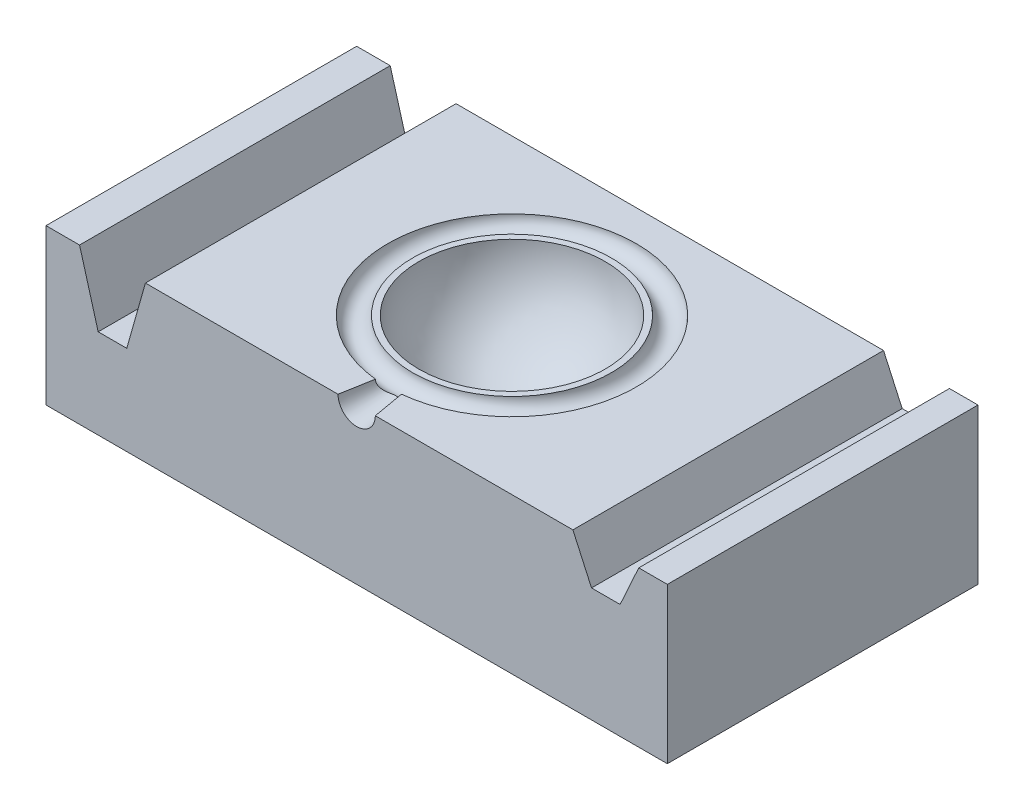
SolidWorks part; units mm, degrees
ref_plane "Plan de face" through (0, 0, 0) normal (0, 0, 1) x (1, 0, 0)
ref_plane "Plan de dessus" through (0, 0, 0) normal (0, 1, 0) x (1, 0, 0)
ref_plane "Plan de droite" through (0, 0, 0) normal (1, 0, 0) x (0, 0, -1)
sketch "Esquisse1" plane through (0, 0, 0) normal (0, 1, 0) x (1, 0, 0)
  line L1 (-25, 12.5) -> (25, 12.5)
  line L2 (-25, 12.5) -> (-25, -12.5)
  line L3 (-25, -12.5) -> (25, -12.5)
  line L4 (25, 12.5) -> (25, -12.5)
  dimension "D1" = 50
  dimension "D2" = 25
  dimension "D3" = 25
  dimension "D4" = 12.5
extrude "Boss.-Extru.1" add sketch "Esquisse1" along normal blind 12.5
sketch "Esquisse3" plane through (0, 0, 0) normal (0, 0, 1) x (1, 0, 0)
  line L0 (-25, 12.5) -> (25, 12.5) construction
  line L1 (0, 20) -> (0, 5)
  arc A0 (0, 20) -> (0, 5) centre (0, 12.5) ccw
  point P5 (0, 12.5)
  dimension "D1" = 7.5
ref_axis "Axe1" through (0, 20, 0) along (0, -1, 0)
revolve "Enlèvement de matière-Révolution1" cut sketch "Esquisse3" angle 360 about axis through (0, 20, 0) along (0, -1, 0)
sketch "Esquisse4" plane through (0, 0, 0) normal (0, 0, 1) x (1, 0, 0)
  line L0 (-25, 12.5) -> (25, 12.5) construction
  line L1 (8, 12.5) -> (10, 12.5)
  arc A0 (10, 12.5) -> (8, 12.5) centre (9, 12.5) cw
  point P3 (0, 12.5)
  dimension "D1" = 1
  dimension "D2" = 9
revolve "Enlèvement de matière-Révolution3" cut sketch "Esquisse4" angle 360 about axis through (0, 20, 0) along (0, -1, 0)
sketch "Esquisse5" plane through (0, 0, 12.5) normal (0, 0, 1) x (1, 0, 0)
  line L0 (-25, 12.5) -> (25, 12.5) construction
  circle A0 centre (0, 12.5) radius 1.5
  dimension "D1" = 3
extrude "Enlèv. mat.-Extru.2" cut sketch "Esquisse5" against normal blind 4 draft 10
sketch "Esquisse6" plane through (0, 0, -12.5) normal (0, 0, -1) x (-1, 0, 0)
  line L0 (22.3, 12.5) -> (20.8, 7.2)
  line L1 (20.8, 7.2) -> (18.5, 7.2)
  line L2 (18.5, 7.2) -> (17, 12.5)
  line L3 (-25, 12.5) -> (25, 12.5) construction
  line L4 (17, 12.5) -> (22.3, 12.5)
  line L5 (-22.7, 12.5) -> (-21.2, 9.2)
  line L6 (-21.2, 9.2) -> (-18.9, 9.2)
  line L7 (-18.9, 9.2) -> (-17.4, 12.5)
  line L8 (-17.4, 12.5) -> (-22.7, 12.5)
  dimension "D1" = 2.7
  dimension "D2" = 2.3
  dimension "D3" = 5.3
  dimension "D4" = 1.5
  dimension "D5" = 5.3
  dimension "D6" = 3.3
  dimension "D7" = 2.3
  dimension "D8" = 5.3
  dimension "D9" = 2.3
  dimension "D10" = 1.5
extrude "Enlèv. mat.-Extru.3" cut sketch "Esquisse6" against normal up to surface (25 mm away) up to face at (0, 8.0833, 12.5)
